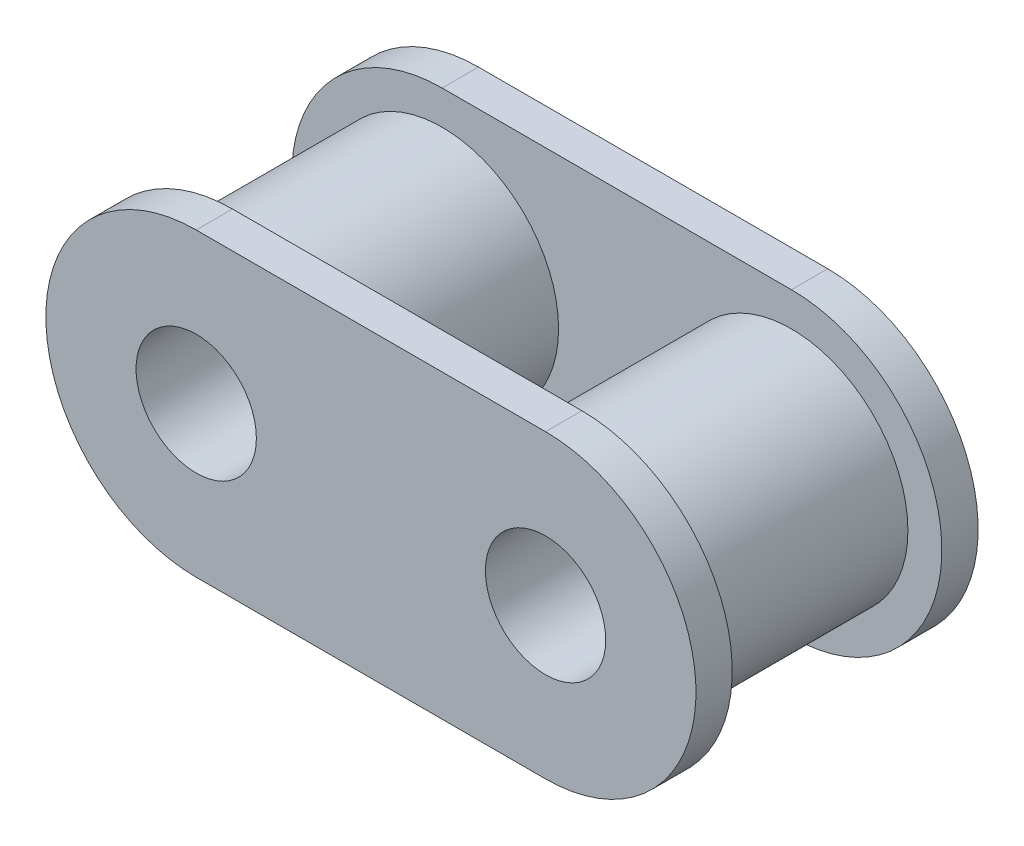
SolidWorks part; units mm, degrees
material "AISI 304"
ref_plane "Plane1" through (0, 0, 0) normal (0, 0, 1) x (1, 0, 0)
ref_plane "Plane2" through (0, 0, 0) normal (0, 1, 0) x (1, 0, 0)
ref_plane "Plane3" through (0, 0, 0) normal (1, 0, 0) x (0, 0, -1)
sketch "Sketch1" plane through (0, 0, 0) normal (0, 0, 1) x (1, 0, 0)
  line L0 (4.7625, 2.6926) -> (4.7625, -2.6926) construction
  line L1 (0, 4.1) -> (9.525, 4.1)
  line L2 (0, -4.1) -> (9.525, -4.1)
  arc A0 (0, 4.1) -> (0, -4.1) centre (0, 0) ccw
  circle A4 centre (0, 0) radius 1.64
  arc A8 (9.525, 4.1) -> (9.525, -4.1) centre (9.525, 0) cw
  circle A9 centre (9.525, 0) radius 1.64
  dimension "D1" = 8.2
  dimension "D2" = 4.7625
  dimension "D6" = 3.28
extrude "Boss-Extrude1" add sketch "Sketch1" along normal blind 0.99
sketch "Sketch2" plane through (0, 0, 0.99) normal (0, 0, 1) x (1, 0, 0)
  circle A0 centre (0, 0) radius 3.175
  circle A2 centre (9.525, 0) radius 3.175
  circle M2 centre (0, 0) radius 1.64
  circle M7 centre (9.525, 0) radius 1.64
  dimension "D1" = 6.35
  dimension "D2" = 6.35
extrude "Boss-Extrude2" add sketch "Sketch2" along normal blind 6.705 contours A2 M7 | A0 M2 region at (-3.0852, 0, 0.99) region at (6.4398, 0, 0.99)
ref_plane "Plane4" through (0, 0, 3.8475) normal (0, 0, -1) x (-1, 0, 0)
mirror "Mirror1" about plane through (0, 0, 3.8475) normal (0, 0, -1) of bodies 105 104
